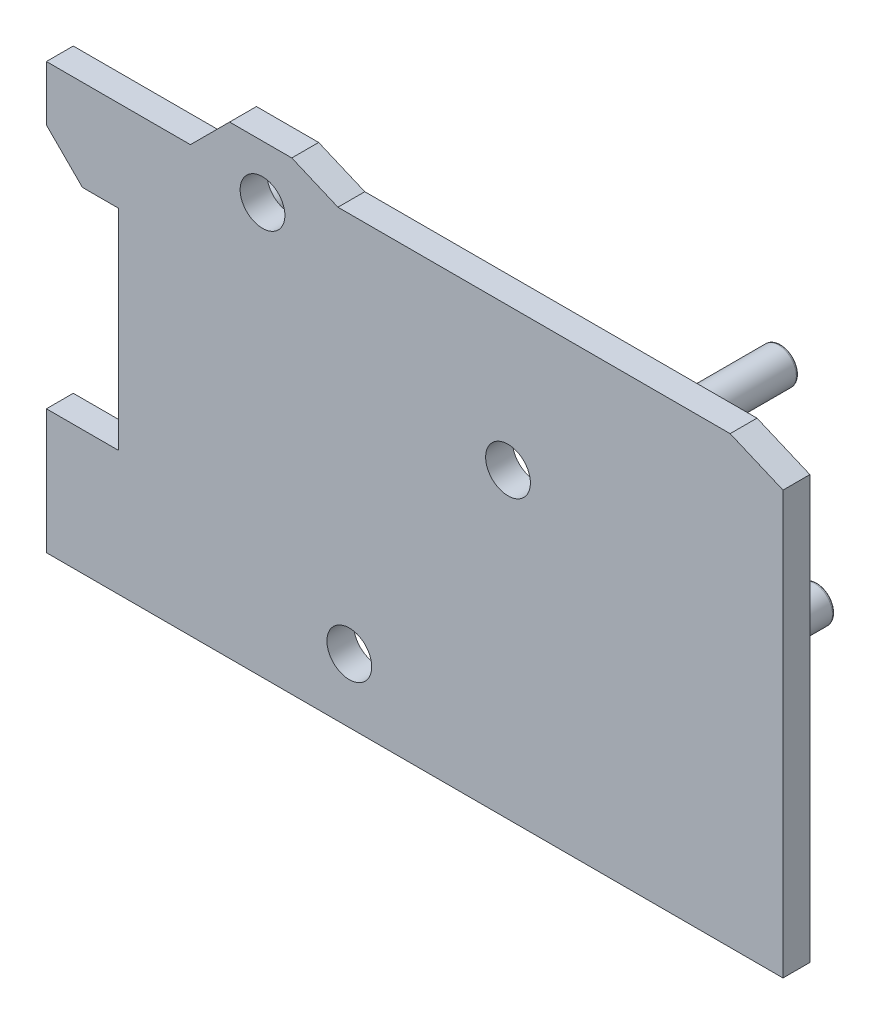
SolidWorks part; units mm, degrees
ref_plane "정면" through (0, 0, 0) normal (0, 0, 1) x (1, 0, 0)
ref_plane "윗면" through (0, 0, 0) normal (0, 1, 0) x (1, 0, 0)
ref_plane "우측면" through (0, 0, 0) normal (1, 0, 0) x (0, 0, -1)
sketch "스케치2" plane through (0, 0, 0) normal (0, 0, 1) x (1, 0, 0)
  line L0 (-41.986, 21.4677) -> (-25.9008, 21.4677)
  line L1 (-25.9008, 21.4677) -> (-21.5254, 25.8432)
  line L2 (-21.5254, 25.8432) -> (-14.5764, 25.8432)
  line L3 (-14.5764, 25.8432) -> (-9.4218, 23.6554)
  line L4 (-9.4218, 23.6554) -> (34.3842, 23.6554)
  line L5 (34.3842, 23.6554) -> (40.2906, 21.1486)
  line L6 (40.2906, 21.1486) -> (40.2906, -26.0481)
  line L7 (40.2906, -26.0481) -> (-41.986, -26.0481)
  line L8 (-41.986, -26.0481) -> (-41.986, -12.1234)
  line L9 (-41.986, -12.1234) -> (-33.9434, -12.1234)
  line L10 (-33.9434, -12.1234) -> (-33.9434, 11.3014)
  line L11 (-33.9434, 11.3014) -> (-37.9647, 11.3014)
  line L12 (-37.9647, 11.3014) -> (-41.986, 15.3227)
  line L13 (-41.986, 15.3227) -> (-41.986, 21.4677)
  line L14 (24.6957, -6.2695) -> (30.5742, -6.2695)
  line L15 (31.5742, -5.2695) -> (31.5742, 0.609)
  line L16 (31.2814, -5.9766) -> (25.9521, -0.6474) construction
  line L17 (-0.8477, -0.8025) -> (-17.8477, -0.8025) construction
  line L18 (-17.8477, -0.8025) -> (-17.8477, 19.8975) construction
  circle A0 centre (-17.8477, 19.8975) radius 2.5
  circle A1 centre (-29.1621, 7.8743) radius 4
  circle A2 centre (24.5742, 17.7305) radius 4
  circle A3 centre (-8.1538, -18.91) radius 2.5
  circle A4 centre (9.5742, 7.7305) radius 2.5
  circle A5 centre (-29.1621, 7.8743) radius 2
  circle A6 centre (24.5742, 17.7305) radius 2
  arc A7 (30.4304, 1.5986) -> (23.7061, -5.1256) centre (31.5742, -6.2695) ccw
  arc A8 (30.5742, -6.2695) -> (31.5742, -5.2695) centre (30.5742, -5.2695) ccw
  arc A9 (31.5742, 0.609) -> (30.4304, 1.5986) centre (30.5742, 0.609) ccw
  arc A10 (24.6957, -6.2695) -> (23.7061, -5.1256) centre (24.6957, -5.2695) cw
  circle A11 centre (28.6167, -3.312) radius 2
  dimension "D1" = 1
  dimension "D5" = 5
  dimension "D6" = 5
  dimension "D7" = 5
  dimension "D12" = 4
  dimension "D13" = 4
  dimension "D14" = 8
  dimension "D15" = 8
  dimension "D18" = 4
  dimension "D2" = 30
  dimension "D3" = 40
  dimension "D4" = 32
  dimension "D8" = 20.7
  dimension "D9" = 17
  dimension "D10" = 10
  dimension "D11" = 15
  dimension "D16" = 22
  dimension "D17" = 14
extrude "보스-돌출11" add sketch "스케치2" along normal blind 3 contours A5 | A1 A5 | L13 L12 L11 L10 L9 L8 L7 L6 L5 L4 L3 L2 L1 L0 A4 A3 A2 A1 A0 L14 A10 A7 A9 L15 A8 | A2 A6 | A6 | A11 | A10 L14 A8 L15 A9 A7 A11 region at (1.0264, -1.8236, 0) region at (24.0237, -5.8509, 0) region at (-33.049, 7.8743, 0) region at (20.6874, 17.7305, 0) region at (-29.1621, 7.8743, 0) region at (24.5742, 17.7305, 0) region at (28.6167, -3.312, 0)
extrude "보스-돌출12" add sketch "스케치2<16>" against normal blind 0.5 contours A1 A5 | A2 A6 | A10 L14 A8 L15 A9 A7 A11 region at (24.0237, -5.8509, 0) region at (-33.049, 7.8743, 0) region at (20.6874, 17.7305, 0)
sketch "스케치2<16>" plane through (0, 0, 0) normal (0, 0, 1) x (1, 0, 0) same geometry as "스케치2"
extrude "보스-돌출13" add sketch "스케치2<17>" against normal blind 12.5 contours A11 | A6 | A5 region at (-29.1621, 7.8743, 0) region at (24.5742, 17.7305, 0) region at (28.6167, -3.312, 0)
sketch "스케치2<17>" plane through (0, 0, 0) normal (0, 0, 1) x (1, 0, 0) same geometry as "스케치2"
fillet "필렛1" radius 0.3 3 edges at (30.6167, -3.312, -12.5) (26.5742, 17.7305, -12.5) (-27.1621, 7.8743, -12.5)
